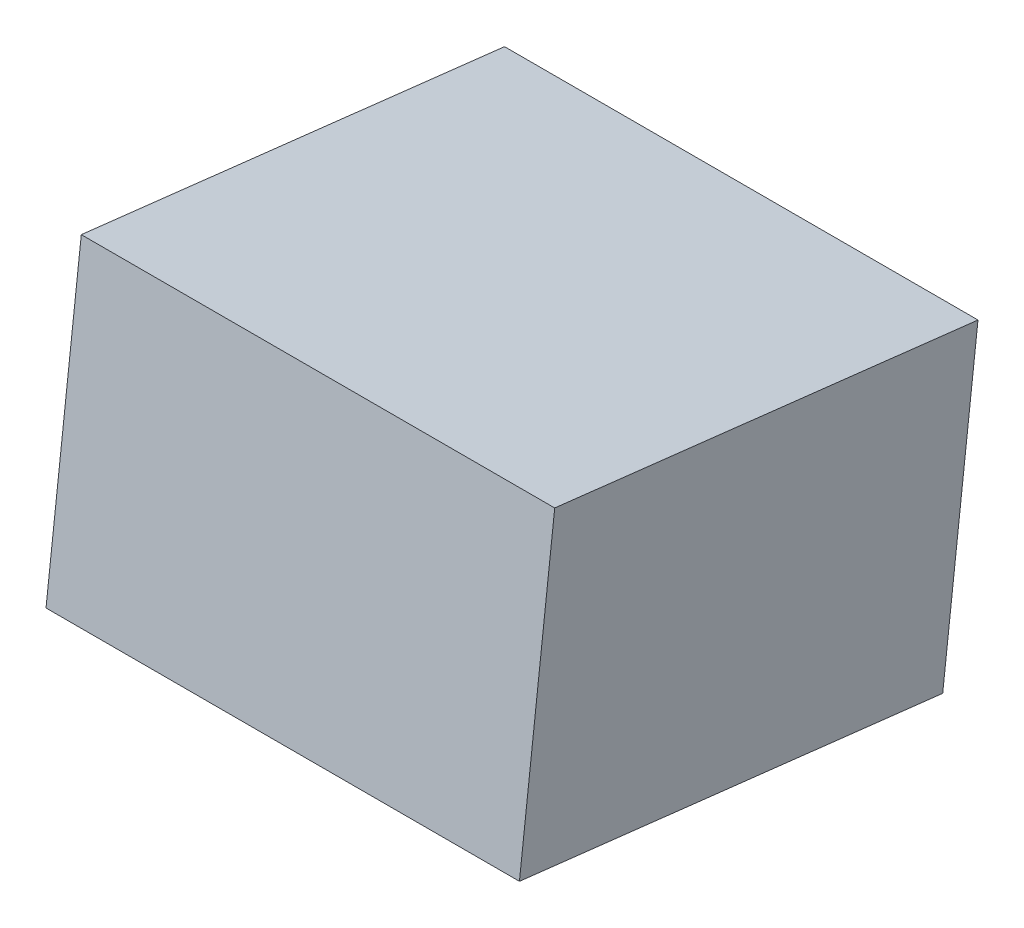
SolidWorks part; units mm, degrees
ref_plane "Front Plane" through (0, 0, 0) normal (0, 0, 1) x (1, 0, 0)
ref_plane "Top Plane" through (0, 0, 0) normal (0, 1, 0) x (1, 0, 0)
ref_plane "Right Plane" through (0, 0, 0) normal (1, 0, 0) x (0, 0, -1)
sketch "Sketch1" plane through (0, 343.9788, -39.7026) normal (0, 0.9934, -0.1147) x (1, 0, 0)
  line L1 (-245, 60.2443) -> (-45, 60.2443)
  line L2 (-245, 60.2443) -> (-245, 240.2443)
  line L3 (-245, 240.2443) -> (-45, 240.2443)
  line L4 (-45, 60.2443) -> (-45, 240.2443)
  line L5 (-245, 60.2443) -> (-45, 240.2443) construction
  line L6 (-245, 240.2443) -> (-45, 60.2443) construction
  point P0 (-145, 150.2443)
  dimension "D1" = 180
  dimension "D2" = 200
extrude "Boss-Extrude1" add sketch "Sketch1" along normal blind 130
